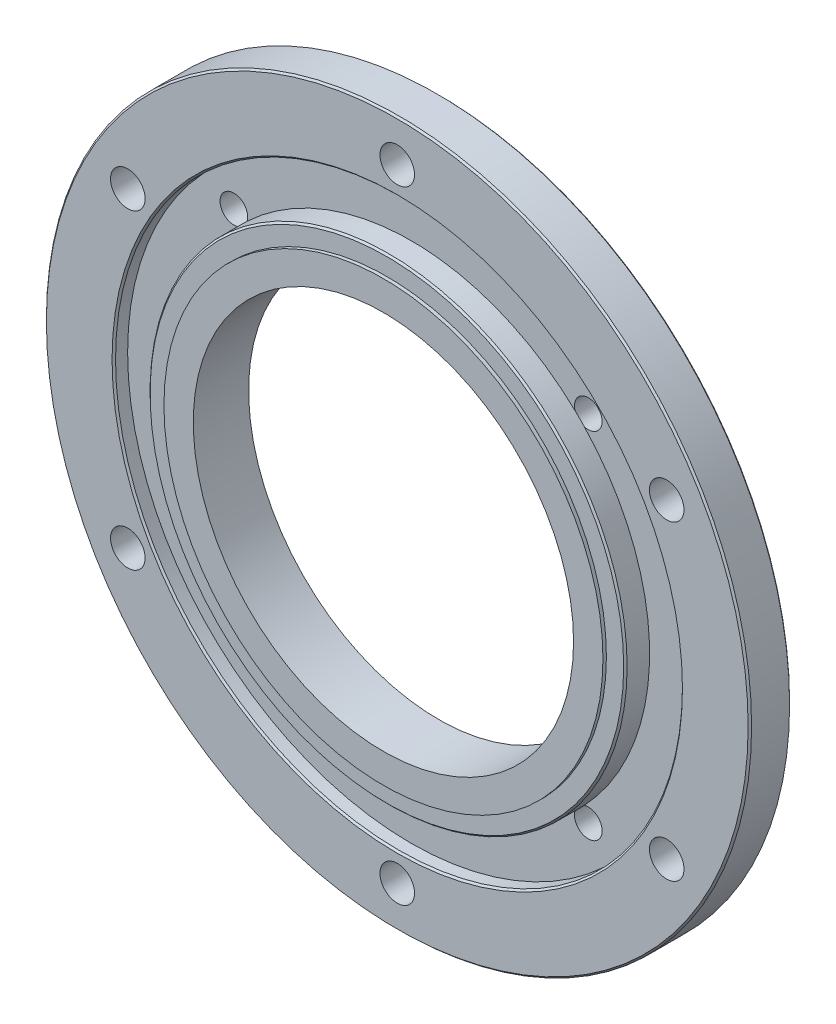
SolidWorks part; units mm, degrees
ref_plane "前视基准面" through (0, 0, 0) normal (0, 0, 1) x (1, 0, 0)
ref_plane "上视基准面" through (0, 0, 0) normal (0, 1, 0) x (1, 0, 0)
ref_plane "右视基准面" through (0, 0, 0) normal (1, 0, 0) x (0, 0, -1)
other "Configuration Table"
sketch "草图1" plane through (0, 0, 0) normal (0, 0, 1) x (1, 0, 0)
  circle A0 centre (0, 0) radius 102
  dimension "D1" = 204
extrude "凸台-拉伸1" add sketch "草图1" along normal blind 12
sketch "草图2" plane through (0, 0, 12) normal (0, 0, 1) x (1, 0, 0)
  circle A0 centre (0, 0) radius 69
  dimension "D1" = 138
extrude "凸台-拉伸2" add sketch "草图2" along normal blind 3
sketch "草图3" plane through (0, 0, 15) normal (0, 0, 1) x (1, 0, 0)
  circle A0 centre (0, 0) radius 63.5
  dimension "D1" = 127
extrude "凸台-拉伸3" add sketch "草图3" along normal blind 1
sketch "草图4" plane through (0, 0, 16) normal (0, 0, 1) x (1, 0, 0)
  circle A0 centre (0, 0) radius 55
  dimension "D1" = 110
extrude "切除-拉伸1" cut sketch "草图4" against normal through all
sketch "草图5" plane through (0, 0, 16) normal (0, 0, 1) x (1, 0, 0)
  circle A0 centre (0, 0) radius 82
  circle A1 centre (0, 0) radius 69 construction
  circle A2 centre (0, 0) radius 69
  dimension "D1" = 164
extrude "切除-拉伸2" cut sketch "草图5" against normal blind 4 from surface starting at face at (69, 0, 12)
sketch "草图6" plane through (0, 0, 0) normal (0, 0, 1) x (1, 0, 0)
  line L0 (0, 0) -> (0, 102) construction
  line L1 (0, 0) -> (55, 0) construction
  circle A0 centre (0, 0) radius 72.5 construction
  circle A1 centre (-51.2652, 51.2652) radius 4
  circle A2 centre (0, 0) radius 102 construction
  circle A3 centre (51.2652, 51.2652) radius 4
  circle A4 centre (0, 0) radius 55 construction
  circle A5 centre (51.2652, -51.2652) radius 4
  circle A6 centre (-51.2652, -51.2652) radius 4
  dimension "D1" = 145
  dimension "D2" = 8
  dimension "D3" = 90
extrude "切除-拉伸3" cut sketch "草图6" along normal blind 8
sketch "草图7" plane through (0, 0, 0) normal (0, 0, -1) x (-1, 0, 0)
  line L0 (0, 0) -> (0, 90) construction
  line L1 (0, 0) -> (-55, 0) construction
  circle A0 centre (0, 0) radius 90 construction
  circle A1 centre (-77.9423, 45) radius 5
  circle A2 centre (0, 0) radius 55 construction
  circle A6 centre (0, 90) radius 5
  circle A7 centre (77.9423, 45) radius 5
  circle A8 centre (77.9423, -45) radius 5
  circle A9 centre (0, -90) radius 5
  circle A10 centre (-77.9423, -45) radius 5
  point P11 (66.4946, 36.66)
  point P12 (0, 0)
  point P22 (0, 0)
  dimension "D1" = 180
  dimension "D2" = 10
  dimension "D3" = 60
  dimension "D4" = 6
extrude "切除-拉伸4" cut sketch "草图7" against normal through all
chamfer "倒角1" distance 0.5 angle 45 4 edges at (82, 0, 12) (69, 0, 15) (102, 0, 12) (102, 0, 0)
